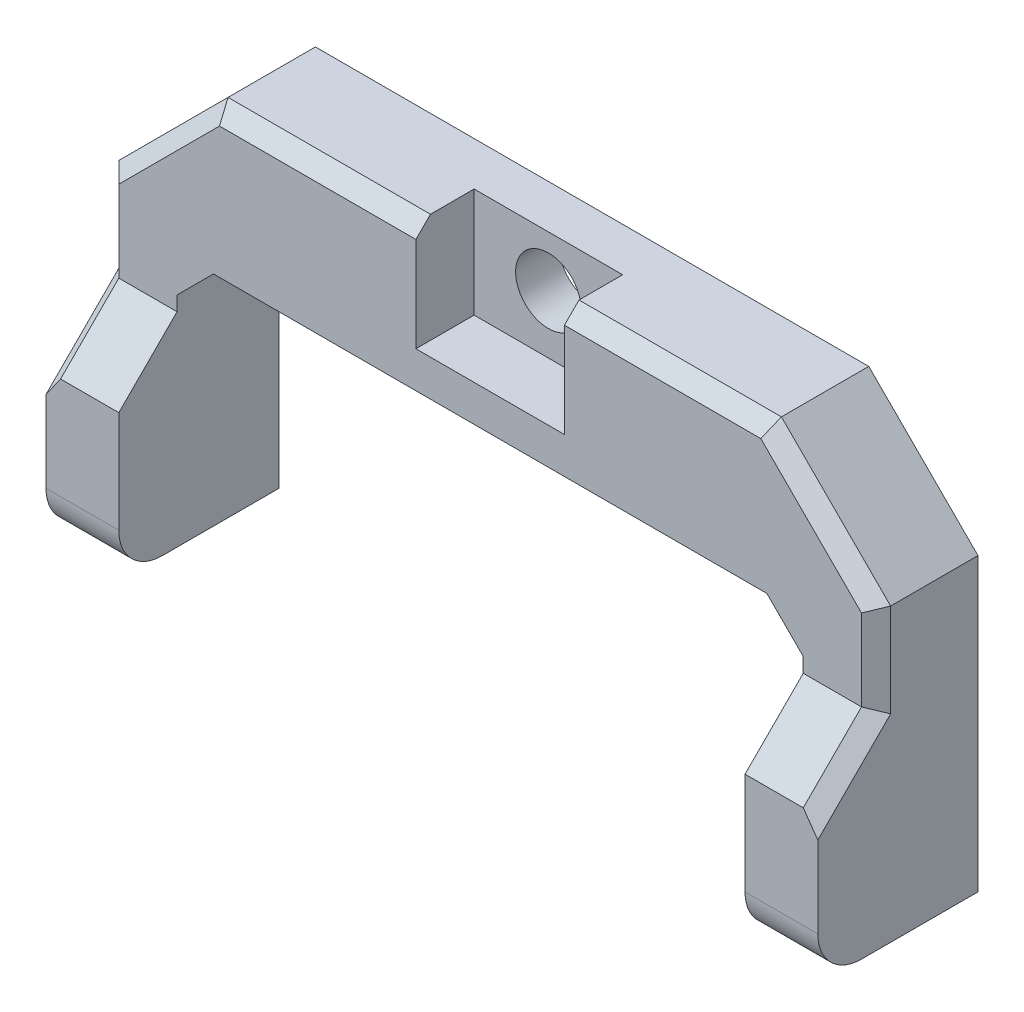
SolidWorks part; units mm, degrees
ref_plane "Front Plane" through (0, 0, 0) normal (0, 0, 1) x (1, 0, 0)
ref_plane "Top Plane" through (0, 0, 0) normal (0, 1, 0) x (1, 0, 0)
ref_plane "Right Plane" through (0, 0, 0) normal (1, 0, 0) x (0, 0, -1)
sketch "Sketch1" plane through (0, 0, 0) normal (0, 0, 1) x (1, 0, 0)
  line L0 (0, 0) -> (0, -10)
  line L1 (0, -10) -> (-19, -10)
  line L2 (-19, -10) -> (-21.5, -12.5)
  line L3 (-21.5, -12.5) -> (-21.5, -27.5)
  line L4 (-21.5, -27.5) -> (-26.5, -27.5)
  line L5 (-26.5, -27.5) -> (-26.5, -7.5)
  line L6 (-26.5, -7.5) -> (-19, 0)
  line L7 (-19, 0) -> (0, 0)
  dimension "D1" = 135
  dimension "D2" = 21.5
  dimension "D3" = 5
  dimension "D4" = 15
  dimension "D5" = 10
  dimension "D6" = 2.5
extrude "Boss-Extrude1" add sketch "Sketch1" along normal blind 7
sketch "Sketch6" plane through (0, 0, 7) normal (0, 0, 1) x (1, 0, 0)
  line L0 (-21.5, -27.5) -> (-21.5, -12.5) construction
  line L1 (-26.5, -27.5) -> (-21.5, -27.5)
  line L2 (-26.5, -27.5) -> (-26.5, -17.5)
  line L3 (-26.5, -17.5) -> (-21.5, -17.5)
  line L4 (-21.5, -27.5) -> (-21.5, -17.5)
  dimension "D1" = 10
extrude "Boss-Extrude2" add sketch "Sketch6" along normal blind 4
sketch "Sketch3" plane through (0, 0, 7) normal (0, 0, 1) x (1, 0, 0)
  line L1 (0, 0) -> (-5.1, 0)
  line L2 (0, 0) -> (0, -7.5)
  line L3 (0, -7.5) -> (-5.1, -7.5)
  line L4 (-5.1, 0) -> (-5.1, -7.5)
  dimension "D1" = 7.5
  dimension "D2" = 5.1
extrude "Cut-Extrude1" cut sketch "Sketch3" against normal blind 4
mirror "Mirror1" about plane through (0, 0, 7) normal (-1, 0, 0) of "Boss-Extrude2", "Boss-Extrude1", "Cut-Extrude1"
hole_wizard "M4 Clearance Hole1" positions "Sketch4" profile "Sketch5" hole size "M4" standard "ANSI Metric" end condition through all
sketch "Sketch4" plane through (0, 0, 3) normal (0, 0, 1) x (1, 0, 0)
  line L0 (-5.1, -7.5) -> (5.1, -7.5) construction
  line L1 (0, -3.85) -> (0, 3.85) construction
  point P0 (0, -3.5)
  dimension "D1" = 4
sketch "Sketch5" plane through (0, -3.5, 3) normal (1, 0, 0) x (0, -1, 0)
  line L0 (0, 0) -> (0, 3)
  line L1 (0, 3) -> (2.25, 3)
  line L2 (2.25, 3) -> (2.25, 0)
  line L5 (2.25, 0) -> (0, 0)
  line L11 (0, -6.35) -> (0, 107.95) construction
  dimension "Thru Hole Dia." = 4.5
  dimension "Thru Hole Depth" = 3
chamfer "Chamfer2" distance 4 2 edges at (24, -17.5, 7) (-24, -17.5, 7)
chamfer "Chamfer4" distance 1 angle 45 8 edges at (26.5, -10.5, 7) (22.75, -3.75, 7) (12.05, 0, 7) (-26.5, -10.5, 7) (-22.75, -3.75, 7) (-12.05, 0, 7) (26.5, -15.5, 9) (-26.5, -15.5, 9)
fillet "Fillet2" radius 3 2 edges at (24, -27.5, 11) (-24, -27.5, 11)
equation "\"a\"=1"
